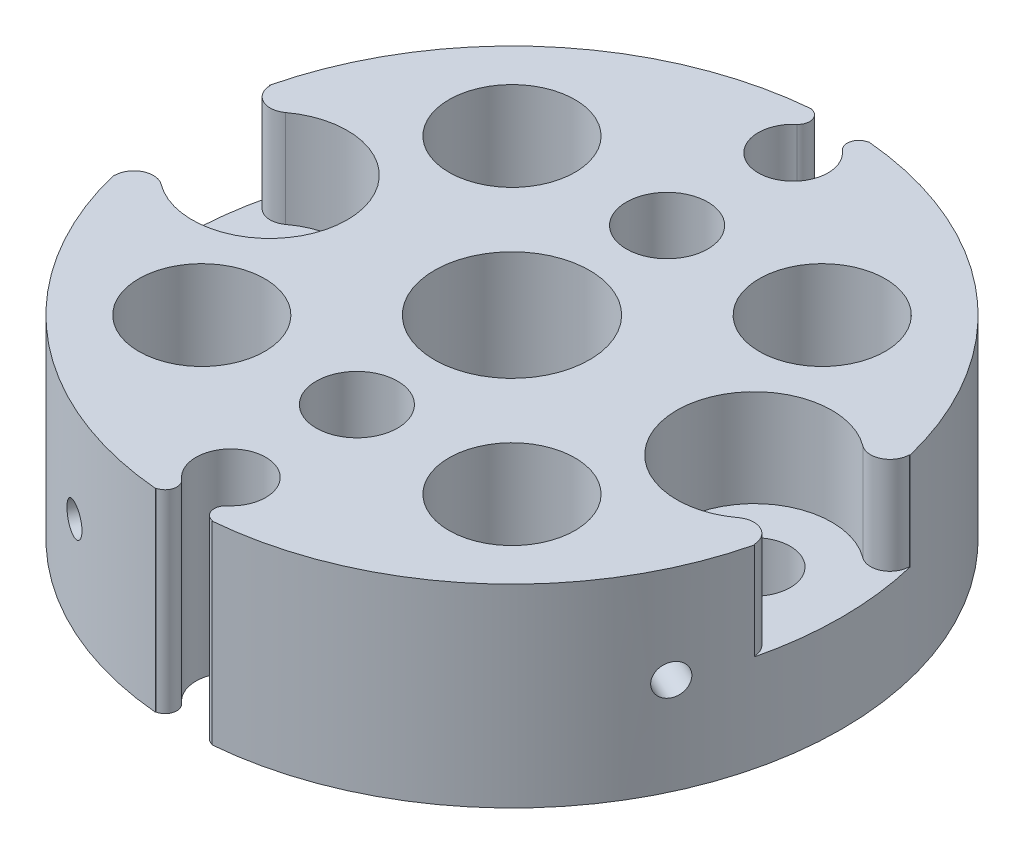
SolidWorks part; units mm, degrees
note: '?' marks a value the reader was unsure of.
material "Brass"
ref_plane "Front Plane" through (0, 0, 0) normal (0, 0, 1) x (1, 0, 0)
ref_plane "Top Plane" through (0, 0, 0) normal (0, 1, 0) x (1, 0, 0)
ref_plane "Right Plane" through (0, 0, 0) normal (1, 0, 0) x (0, 0, -1)
sketch "Sketch1" plane through (0, 0, 0) normal (0, 1, 0) x (1, 0, 0)
  circle A0 centre (0, 0) radius 17
  dimension "D1" = 34
extrude "Boss-Extrude1" add sketch "Sketch1" along normal blind 10
hole_wizard "Ø3.7 (3.7) Diameter Hole1" positions "Sketch6" profile "Sketch7" hole size "Ø3.7" standard "DIN" end condition up to next
sketch "Sketch6" plane through (0, 10, 0) normal (0, 1, 0) x (1, 0, 0)
  circle A0 centre (0, 0) radius 17 construction
  point P0 (-12.5, 0)
  point P6 (12.5, 0)
  dimension "D2" = 25
  dimension "D3" = 12.5
  dimension "D1" = 2
sketch "Sketch7" plane through (-12.5, 10, 0) normal (1, 0, 0) x (0, 0, 1)
  line L0 (0, 0) -> (0, 10)
  line L1 (0, 10) -> (1.85, 10)
  line L2 (1.85, 10) -> (1.85, 0)
  line L5 (1.85, 0) -> (0, 0)
  line L11 (0, -6.35) -> (0, 107.95) construction
  dimension "Thru Hole Dia." = 3.7
  dimension "Thru Hole Depth" = 10
sketch "Sketch21" plane through (0, 10, 0) normal (0, 1, 0) x (1, 0, 0)
  circle A0 centre (-8, 8) radius 3.25
  circle A1 centre (8, 8) radius 3.25
  circle A2 centre (8, -8) radius 3.25
  circle A3 centre (-8, -8) radius 3.25
  point P12 (0, 0)
  dimension "D1" = 6.5
  dimension "D2" = 8
  dimension "D3" = 8
hole_wizard "M5 Tapped Hole1" positions "Sketch10" profile "Sketch9" tap size "M5" standard "DIN" end condition up to next
sketch "Sketch10" plane through (0, 10, 0) normal (0, 1, 0) x (1, 0, 0)
  point P0 (0, 8)
  point P2 (0, -8)
  dimension "D1" = 16
  dimension "D2" = 8
sketch "Sketch9" plane through (0, 10, -8) normal (1, 0, 0) x (0, 0, 1)
  line L0 (0, 0) -> (0, 10)
  line L1 (0, 10) -> (2.1, 10)
  line L2 (2.1, 10) -> (2.1, 0)
  line L5 (2.1, 0) -> (0, 0)
  line L11 (0, -6.35) -> (0, 107.95) construction
  dimension "Thru Tap Drill Dia." = 4.2
  dimension "Thru Tap Drill Depth" = 10
cosmetic thread "Hole Thread1" parameters "D2"=5
cosmetic thread "Hole Thread2" parameters "D2"=5
hole_wizard "Ø12.0 (12) Diameter Hole1" positions "Sketch11" profile "Sketch12" hole size "Ø12.0" standard "DIN" end condition up to next
sketch "Sketch11" plane through (0, 10, 0) normal (0, 1, 0) x (1, 0, 0)
  point P0 (0, 0)
sketch "Sketch12" plane through (0, 10, 0) normal (1, 0, 0) x (0, 0, 1)
  line L0 (0, 0) -> (0, 10)
  line L1 (0, 10) -> (4, 10)
  line L2 (4, 10) -> (4, 0)
  line L5 (4, 0) -> (0, 0)
  line L11 (0, -6.35) -> (0, 107.95) construction
  dimension "Thru Hole Dia." = 8
  dimension "Thru Hole Depth" = 10
sketch "Sketch14" plane through (0, 10, 0) normal (0, 1, 0) x (1, 0, 0)
  line L0 (-1.4596, 16.9131) -> (-1.1668, 18.5065)
  line L1 (-1.1668, 18.5065) -> (1.608, 18.3561)
  line L2 (1.608, 18.3561) -> (1.4529, 16.9139)
  line L3 (1.4596, -16.9131) -> (1.1668, -18.5065)
  line L4 (1.1668, -18.5065) -> (-1.608, -18.3561)
  line L5 (-1.608, -18.3561) -> (-1.4529, -16.9139)
  arc A0 (-1.1751, 15.8635) -> (1.1741, 15.8643) centre (0, 14.5) ccw
  arc A1 (1.1751, -15.8635) -> (-1.1741, -15.8643) centre (0, -14.5) ccw
  arc A2 (-1.1751, 15.8635) -> (-1.4596, 16.9131) centre (-1.5686, 16.3202) ccw
  arc A3 (1.4529, 16.9139) -> (1.1741, 15.8643) centre (1.5676, 16.3216) ccw
  arc A4 (1.1751, -15.8635) -> (1.4596, -16.9131) centre (1.5686, -16.3202) ccw
  arc A5 (-1.4529, -16.9139) -> (-1.1741, -15.8643) centre (-1.5676, -16.3216) ccw
  point P20 (0, 0)
  dimension "D1" = 2
sketch "Sketch16" plane through (0, 10, 0) normal (0, 1, 0) x (1, 0, 0)
  line L0 (-16.4878, 4.0156) -> (-18.9608, 4.0156)
  line L1 (-18.9608, 4.0156) -> (-18.9608, -4.0113)
  line L2 (-18.9608, -4.0113) -> (-16.489, -4.0113)
  line L3 (16.4878, -4.0156) -> (18.9608, -4.0156)
  line L4 (18.9608, -4.0156) -> (18.9608, 4.0113)
  line L5 (18.9608, 4.0113) -> (16.489, 4.0113)
  arc A0 (-14.8892, -3.2081) -> (-14.8861, 3.2104) centre (-12.5, 0) ccw
  arc A1 (-16.4878, 4.0156) -> (-14.8861, 3.2104) centre (-15.4845, 4.0156) ccw
  arc A2 (-14.8892, -3.2081) -> (-16.489, -4.0113) centre (-15.4874, -4.0113) ccw
  arc A3 (14.8892, 3.2081) -> (14.8861, -3.2104) centre (12.5, 0) ccw
  arc A4 (16.4878, -4.0156) -> (14.8861, -3.2104) centre (15.4845, -4.0156) ccw
  arc A5 (14.8892, 3.2081) -> (16.489, 4.0113) centre (15.4874, 4.0113) ccw
  point P2 (-5.7645, 0.1684)
  point P10 (-5.7645, 0.1684)
  point P20 (-5.7645, 0.1684)
  point P23 (-12.5, 0)
  point P24 (12.5, 0)
  dimension "D1" = 12.5
  dimension "D2" = 12.5
extrude "Cut-Extrude3" cut sketch "Sketch16" against normal blind 5
sketch "Sketch17" plane through (0, 5, 0) normal (0, 1, 0) x (1, 0, 0)
  line L0 (0, 0) -> (15.4072, -7.1845)
  line L1 (0, 0) -> (19.5385, 0) construction
  arc A0 (-16.52, -4.0113) -> (16.5189, -4.0156) centre (0, 0) ccw construction
  dimension "D1" = 25
hole_wizard "M2 Tapped Hole1" positions "3DSketch1" profile "Sketch18" tap size "M2" standard "DIN"
sketch3d "3DSketch1"
  point P0 (0, 0, 0)
  point P3 (15.4072, 5, 7.1845)
sketch "Sketch18" plane through (15.4072, 5, 7.1845) normal (0, 1, 0) x (0.4226, 0, -0.9063)
  line L0 (0, 0) -> (0, 4.4807)
  line L1 (0, 4.4807) -> (0.8, 4)
  line L2 (0.8, 4) -> (0.8, 0)
  line L5 (0.8, 0) -> (0, 0)
  line L10 (0, 4.4807) -> (-0.8, 4) construction
  line L11 (0, -6.35) -> (0, 107.95) construction
  dimension "Tap Drill Dia." = 1.6
  dimension "Tap Drill Depth" = 4
  dimension "Drill Angle" = 118
cosmetic thread "Hole Thread3" parameters "D1"=3, "D2"=2
ref_axis "Axis1" through (0, 0, 0) along (0, 1, 0)?
pattern_circular "CirPattern1" count 4 over 360 about axis through (0, 0, 0) along (0, 1, 0) of "M2 Tapped Hole1"
extrude "Cut-Extrude4" cut sketch "Sketch21" against normal through all
extrude "Cut-Extrude5" cut sketch "Sketch14" against normal through all
